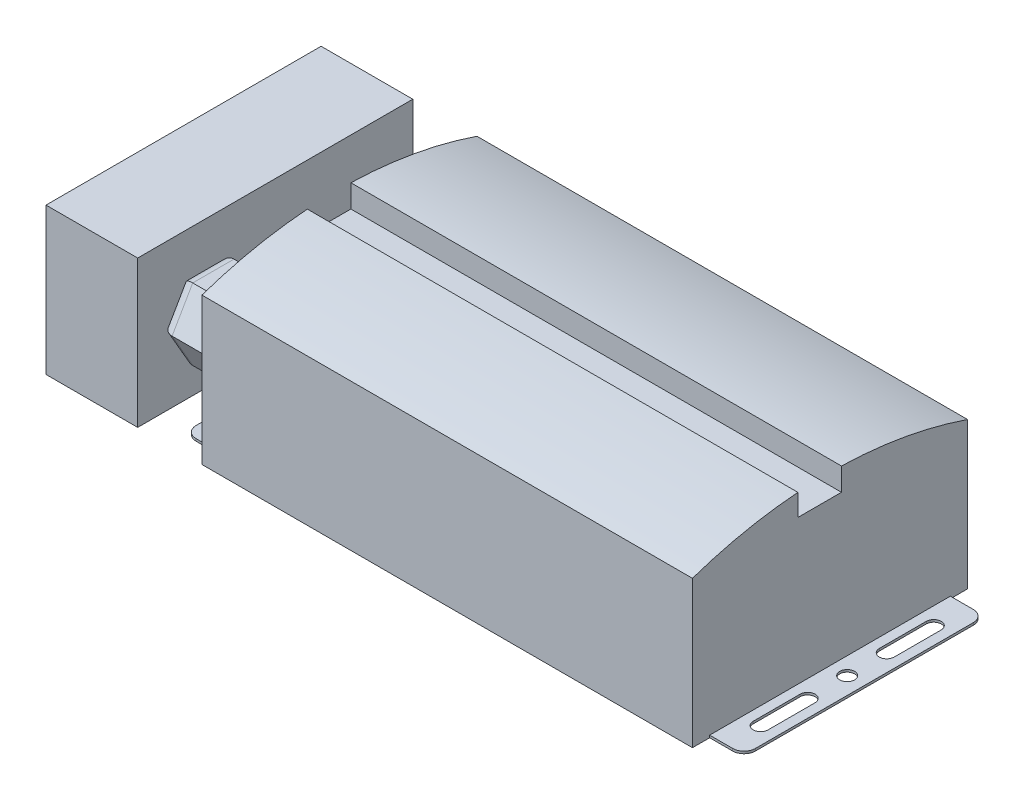
SolidWorks part; units mm, degrees
ref_plane "Спереди" through (0, 0, 0) normal (0, 0, 1) x (1, 0, 0)
ref_plane "Сверху" through (0, 0, 0) normal (0, 1, 0) x (1, 0, 0)
ref_plane "Справа" through (0, 0, 0) normal (1, 0, 0) x (0, 0, -1)
sketch "Эскиз1" plane through (0, 0, 0) normal (1, 0, 0) x (0, 0, -1)
  line L0 (-60, 0) -> (60, 0)
  line L1 (60, 0) -> (60, 64)
  line L2 (5, 64) -> (-14, 64)
  line L3 (-60, 64) -> (-60, 0)
  line L4 (-14, 64) -> (-14, 73.4695)
  line L6 (5, 73.9324) -> (5, 64)
  arc A0 (-60, 64) -> (-14, 73.4695) centre (0, -111) cw
  arc A1 (5, 73.9324) -> (60, 64) centre (0, -111) cw
  point P7 (0, 0)
  point P9 (0, 0)
  dimension "D1" = 120
  dimension "D2" = 64
  dimension "D3" = 74
  dimension "D4" = 55
  dimension "D5" = 19
extrude "Бобышка-Вытянуть1" add sketch "Эскиз1" along normal blind 214
sketch "Эскиз2" plane through (0, 0, 0) normal (-1, 0, 0) x (0, 0, 1)
  line L0 (60, 32) -> (-60, 32) construction
  line L1 (50, 32) -> (41, 47.5885)
  line L2 (41, 47.5885) -> (23, 47.5885)
  line L3 (23, 47.5885) -> (14, 32)
  line L4 (14, 32) -> (23, 16.4115)
  line L5 (23, 16.4115) -> (41, 16.4115)
  line L6 (41, 16.4115) -> (50, 32)
  line L7 (60, 64) -> (60, 0) construction
  line L8 (-60, 0) -> (-60, 64) construction
  line L10 (-19, 32) -> (-25.25, 42.8253)
  line L11 (-25.25, 42.8253) -> (-37.75, 42.8253)
  line L12 (-37.75, 42.8253) -> (-44, 32)
  line L13 (-44, 32) -> (-37.75, 21.1747)
  line L14 (-37.75, 21.1747) -> (-25.25, 21.1747)
  line L15 (-25.25, 21.1747) -> (-19, 32)
  circle A0 centre (32, 32) radius 15.5885 construction
  circle A1 centre (-31.5, 32) radius 10.8253 construction
  point P14 (0, 0)
  point P15 (0, 0)
  dimension "D1" = 36
  dimension "D2" = 46
  dimension "D3" = 25
  dimension "D4" = 41
extrude "Бобышка-Вытянуть2" add sketch "Эскиз2" along normal blind 23 contours L12 L13 L14 L15 L10 L11
extrude "Бобышка-Вытянуть3" add sketch "Эскиз2<3>" along normal blind 28 contours L2 L3 L4 L5 L6 L1
sketch "Эскиз2<3>" plane through (0, 0, 0) normal (-1, 0, 0) x (0, 0, 1) same geometry as "Эскиз2"
fillet "Скругление1" radius 5 12 edges at (-28, 24.2058, 45.5) (-28, 16.4115, 32) (-28, 24.2058, 18.5) (-28, 39.7942, 18.5) (-28, 47.5885, 32) (-28, 39.7942, 45.5) (-23, 26.5873, -40.875) (-23, 21.1747, -31.5) (-23, 26.5873, -22.125) (-23, 37.4127, -22.125) (-23, 42.8253, -31.5) (-23, 37.4127, -40.875)
sketch "Эскиз4" plane through (0, 0, 0) normal (0, -1, 0) x (1, 0, 0)
  line L0 (107, -1060) -> (107, 48940) construction
  line L1 (-15, 52.5) -> (229, 52.5)
  line L2 (-15, 52.5) -> (-15, -52.5)
  line L3 (-15, -52.5) -> (229, -52.5)
  line L4 (229, 52.5) -> (229, -52.5)
  line L5 (214, -60) -> (0, -60) construction
  line L6 (-1000, 0) -> (49000, 0) construction
  line L7 (0, 60) -> (0, -60) construction
  line L8 (221.5, -970.5815) -> (221.5, 49029.4185) construction
  line L9 (221.5, 37.75) -> (221.5, 17.25) construction
  line L10 (224.75, 37.75) -> (224.75, 17.25)
  line L11 (218.25, 37.75) -> (218.25, 17.25)
  line L12 (221.5, -37.75) -> (221.5, -17.25) construction
  line L13 (224.75, -37.75) -> (224.75, -17.25)
  line L14 (218.25, -37.75) -> (218.25, -17.25)
  line L15 (-7.5, 37.75) -> (-7.5, 17.25) construction
  line L16 (-10.75, 37.75) -> (-10.75, 17.25)
  line L17 (-4.25, 37.75) -> (-4.25, 17.25)
  line L18 (-7.5, -37.75) -> (-7.5, -17.25) construction
  line L19 (-10.75, -37.75) -> (-10.75, -17.25)
  line L20 (-4.25, -37.75) -> (-4.25, -17.25)
  circle A0 centre (221.5, 0) radius 3.25
  arc A1 (224.75, 37.75) -> (218.25, 37.75) centre (221.5, 37.75) ccw
  arc A2 (218.25, 17.25) -> (224.75, 17.25) centre (221.5, 17.25) ccw
  arc A3 (224.75, -37.75) -> (218.25, -37.75) centre (221.5, -37.75) cw
  arc A4 (218.25, -17.25) -> (224.75, -17.25) centre (221.5, -17.25) cw
  circle A5 centre (-7.5, 0) radius 3.25
  arc A6 (-10.75, 37.75) -> (-4.25, 37.75) centre (-7.5, 37.75) cw
  arc A7 (-4.25, 17.25) -> (-10.75, 17.25) centre (-7.5, 17.25) cw
  arc A8 (-10.75, -37.75) -> (-4.25, -37.75) centre (-7.5, -37.75) ccw
  arc A9 (-4.25, -17.25) -> (-10.75, -17.25) centre (-7.5, -17.25) ccw
  point P9 (107, -60)
  point P10 (-15, 0)
  point P13 (107, -52.5)
  point P20 (221.5, 27.5)
  point P28 (221.5, 41)
  point P30 (221.5, -27.5)
  point P39 (-7.5, 27.5)
  point P46 (-7.5, -27.5)
  point P51 (0, 0)
  dimension "D4" = 6.5
  dimension "D6" = 27
  dimension "D1" = 105
  dimension "D2" = 15
  dimension "D3" = 7.5
  dimension "D5" = 11.5
extrude "Бобышка-Вытянуть4" add sketch "Эскиз4" against normal blind 1
fillet "Скругление2" radius 5 4 edges at (-15, 0.5, -52.5) (-15, 0.5, 52.5) (229, 0.5, -52.5) (229, 0.5, 52.5)
sketch "Эскиз5" plane through (-28, 0, 0) normal (-1, 0, 0) x (0, 0, 1)
  line L0 (60, 64) -> (60, 0) construction
  line L1 (-60, 0) -> (-60, 64) construction
  line L2 (60, 64) -> (60, 0)
  line L3 (-60, 0) -> (-60, 64)
  line L4 (-60, 64) -> (60, 64)
  line L5 (-60, 0) -> (60, 0)
extrude "Бобышка-Вытянуть5" add sketch "Эскиз5" along normal blind 40
